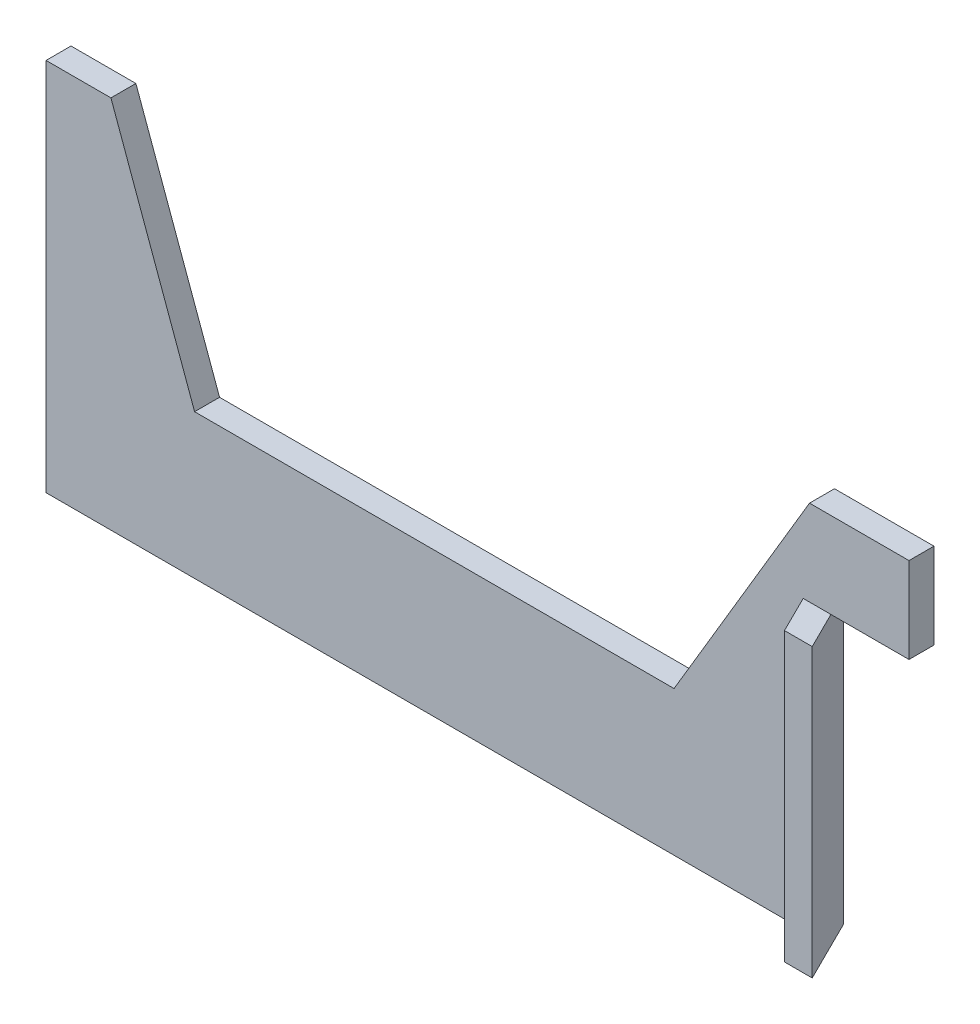
SolidWorks part; units mm, degrees
ref_plane "Front Plane" through (0, 0, 0) normal (0, 0, 1) x (1, 0, 0)
ref_plane "Top Plane" through (0, 0, 0) normal (0, 1, 0) x (1, 0, 0)
ref_plane "Right Plane" through (0, 0, 0) normal (1, 0, 0) x (0, 0, -1)
sketch "Sketch1" plane through (0, 0, 0) normal (0, 0, 1) x (1, 0, 0)
  line L2 (-60.75, -30) -> (-60.75, 30)
  line L11 (63.0497, 16) -> (77.5497, 16)
  line L18 (63.0497, -30) -> (63.0497, 16)
  line L21 (77.5497, 29.7321) -> (77.5497, 16)
  line L23 (-60.75, 30) -> (-50.3529, 30)
  line L24 (-50.3529, 30) -> (-36.9454, -6.8552)
  line L25 (-36.9454, -6.8552) -> (39.8971, -6.8552)
  line L26 (39.8971, -6.8552) -> (61.6068, 29.7321)
  line L27 (61.6068, 29.7321) -> (77.5497, 29.7321)
  line L29 (-60.75, -30) -> (63.0497, -30)
  point P13 (-60.75, 0)
  dimension "D1" = 138.3
  dimension "D2" = 14.5
  dimension "D3" = 46
  dimension "D4" = 60
extrude "Boss-Extrude1" add sketch "Sketch1" along normal mid plane 4
sketch "Sketch2" plane through (0, -30, 0) normal (0, -1, 0) x (1, 0, 0)
  line L0 (63.0497, 2) -> (63.0497, -2) construction
  line L5 (-60.75, 2) -> (63.0497, 2) construction
  line L15 (-60.75, -2) -> (63.0497, -2) construction
  line L18 (63.0497, -2) -> (67.9986, 7.9611)
  line L19 (67.9986, 7.9611) -> (63.556, 7.9611)
  line L20 (63.556, 7.9611) -> (60.5944, 2)
  line L21 (60.5944, 2) -> (63.0497, -2)
  point P0 (67.9986, 7.9611)
extrude "Boss-Extrude2" add sketch "Sketch2" against normal up to surface (46 mm away) up to face at (70.2997, 16, 0)
equation "\"wall_thick_ness\"=4"
equation "\"D1@Boss-Extrude1\"=\"wall_thick_ness\""
equation "\"back_boost\"=7"
equation "\"D1@Sketch1\"=\"back_boost\"+131.30mm"
equation "\"gate\"=11"
equation "\"D2@Sketch1\"=\"gate\"+3.5"
